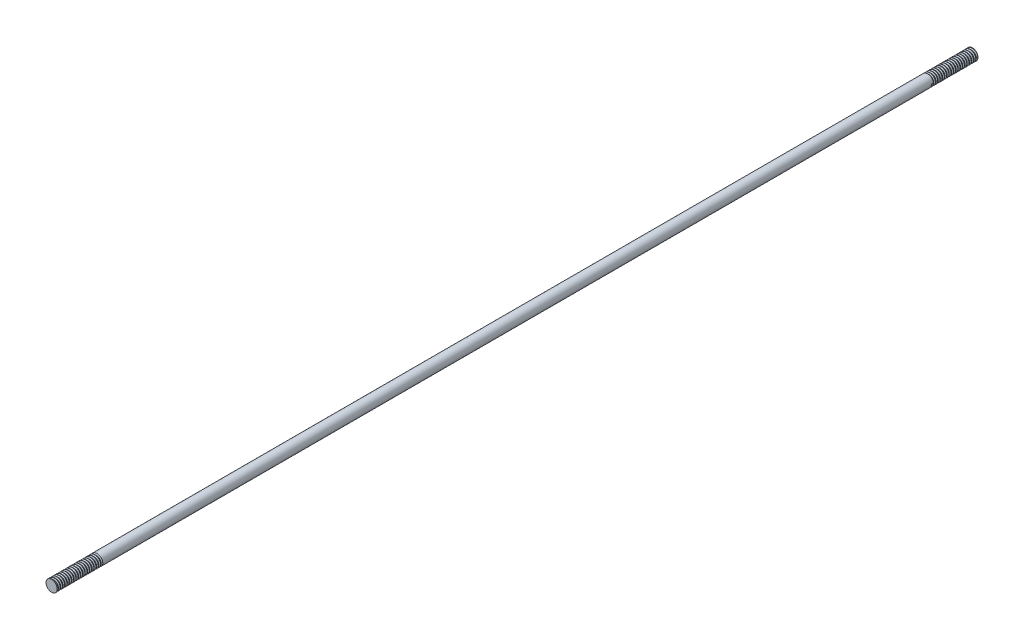
SolidWorks part; units mm, degrees
ref_plane "Front Plane" through (0, 0, 0) normal (0, 0, 1) x (1, 0, 0)
ref_plane "Top Plane" through (0, 0, 0) normal (0, 1, 0) x (1, 0, 0)
ref_plane "Right Plane" through (0, 0, 0) normal (1, 0, 0) x (0, 0, -1)
sketch "Sketch1" plane through (0, 0, 0) normal (0, 0, 1) x (1, 0, 0)
  circle A0 centre (0, 0) radius 3.175
  dimension "D1" = 6.35
extrude "Boss-Extrude1" add sketch "Sketch1" along normal blind 522.435
thread "Thread2" pitch 1.27 method cut profile "Thread Profile1" start angle 2, offset 0, length 25.4, pitch 1.27, diameter 6.35
ref_plane "Plane1" through (3.1731, 0.1108, 0) normal (0.0349, -0.9994, 0) x (0.9994, 0.0349, 0)
sketch "Thread Profile1" plane through (3.1731, 0.1108, 0) normal (0.0349, -0.9994, 0) x (0.9994, 0.0349, 0)
  line L0 (0, 0) -> (0, 1.27) construction
  line L11 (0, 0) -> (0, 1.1112)
  line L12 (0, 1.1112) -> (-0.6874, 0.7144)
  line L13 (-0.6874, 0.7144) -> (-0.6874, 0.3969)
  line L15 (-0.6874, 0.3969) -> (0, 0)
  line L17 (-0.6874, 0.5556) -> (0, 0.5556) construction
  point P2 (0, 0)
  dimension "Pitch" = 1.27
  dimension "Profile_Angle" = 60
  dimension "Profile_Land" = 0.3175
  dimension "Profile_Height" = 0.6874
thread "Thread3" pitch 1.27 method cut profile "Thread Profile2" start angle 2, offset 0, length 25.4, pitch 1.27, diameter 6.35
ref_plane "Plane2" through (-3.1731, 0.1108, 522.435) normal (-0.0349, -0.9994, 0) x (-0.9994, 0.0349, 0)
sketch "Thread Profile2" plane through (-3.1731, 0.1108, 522.435) normal (-0.0349, -0.9994, 0) x (-0.9994, 0.0349, 0)
  line L0 (0, 0) -> (0, 1.27) construction
  line L11 (0, 0) -> (0, 1.1112)
  line L12 (0, 1.1112) -> (-0.6874, 0.7144)
  line L13 (-0.6874, 0.7144) -> (-0.6874, 0.3969)
  line L15 (-0.6874, 0.3969) -> (0, 0)
  line L17 (-0.6874, 0.5556) -> (0, 0.5556) construction
  point P2 (0, 0)
  dimension "Pitch" = 1.27
  dimension "Profile_Angle" = 60
  dimension "Profile_Land" = 0.3175
  dimension "Profile_Height" = 0.6874
ref_axis "Axis1" through (0, 0, 522.435) along (0, 0, -1)
